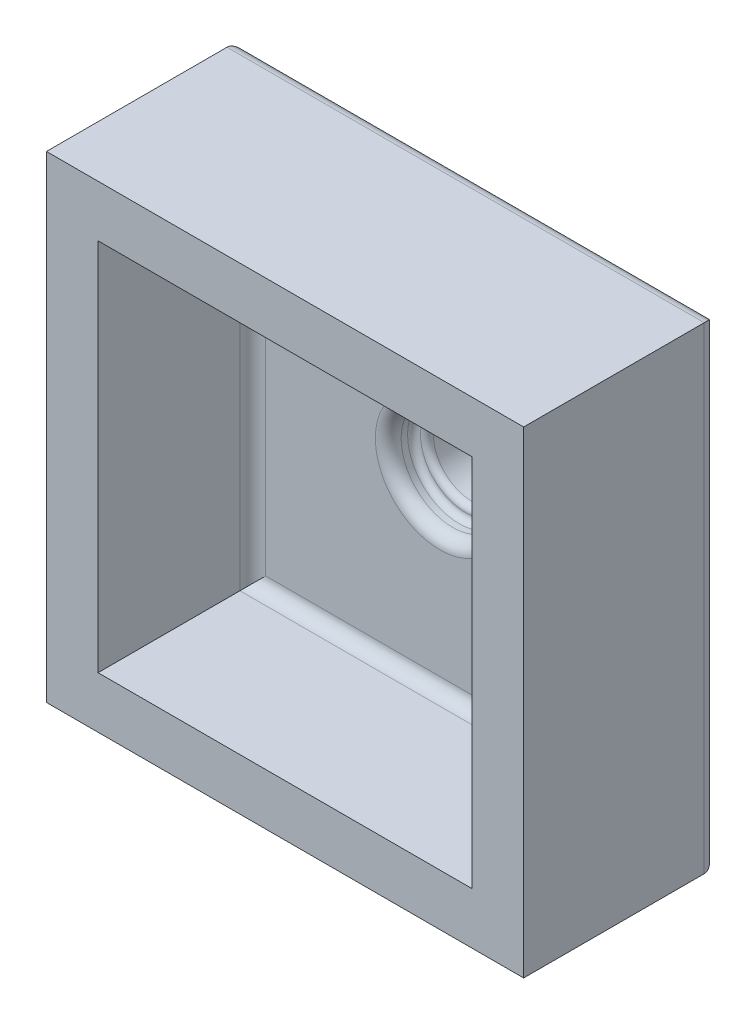
SolidWorks part; units mm, degrees
ref_plane "Front Plane" through (0, 0, 0) normal (0, 0, 1) x (1, 0, 0)
ref_plane "Top Plane" through (0, 0, 0) normal (0, 1, 0) x (1, 0, 0)
ref_plane "Right Plane" through (0, 0, 0) normal (1, 0, 0) x (0, 0, -1)
sketch "Sketch2" plane through (0, 0, 0) normal (0, 0, 1) x (1, 0, 0)
  line L1 (18.5, 18.5) -> (-18.5, 18.5)
  line L2 (18.5, 18.5) -> (18.5, -18.5)
  line L3 (18.5, -18.5) -> (-18.5, -18.5)
  line L4 (-18.5, 18.5) -> (-18.5, -18.5)
  line L5 (18.5, 18.5) -> (-18.5, -18.5) construction
  line L6 (18.5, -18.5) -> (-18.5, 18.5) construction
  point P0 (0, 0)
  dimension "D1" = 37
  dimension "D2" = 37
extrude "Boss-Extrude1" add sketch "Sketch2" along normal blind 15
sketch "Sketch3" plane through (0, 0, 15) normal (0, 0, 1) x (1, 0, 0)
  line L1 (14.5, 14.5) -> (-14.5, 14.5)
  line L2 (14.5, 14.5) -> (14.5, -14.5)
  line L3 (14.5, -14.5) -> (-14.5, -14.5)
  line L4 (-14.5, 14.5) -> (-14.5, -14.5)
  line L5 (14.5, 14.5) -> (-14.5, -14.5) construction
  line L6 (14.5, -14.5) -> (-14.5, 14.5) construction
  point P0 (0, 0)
  dimension "D1" = 29
  dimension "D2" = 29
extrude "Cut-Extrude1" cut sketch "Sketch3" against normal blind 12
sketch "Sketch4" plane through (0, 0, 0) normal (0, 0, -1) x (-1, 0, 0)
  circle A0 centre (0, 0) radius 4
extrude "Cut-Extrude2" cut sketch "Sketch4" against normal blind 12
ref_plane "Plane1" through (0, 0, 1) normal (0, 0, -1) x (-1, 0, 0)
sketch "Sketch5" plane through (0, 0, 1) normal (0, 0, -1) x (-1, 0, 0)
  circle A0 centre (0, 0) radius 4
extrude "Boss-Extrude3" add sketch "Sketch5" along normal blind 12
sketch "Sketch6" plane through (0, 0, -11) normal (0, 0, -1) x (-1, 0, 0)
  circle A0 centre (0, 0) radius 3
extrude "Cut-Extrude3" cut sketch "Sketch6" against normal blind 12
fillet "Fillet3" radius 1 5 edges at (0, -18.5, 0) (18.5, 0, 0) (0, 18.5, 0) (-18.5, 0, 0) (-4, 0, 0)
fillet "Fillet4" radius 1 5 edges at (0, 14.5, 3) (14.5, 0, 3) (0, -14.5, 3) (-14.5, 0, 3) (-4, 0, 3)
fillet "Fillet6" radius 0.5 2 edges at (-4, 0, 1) (-3, 0, 1)
